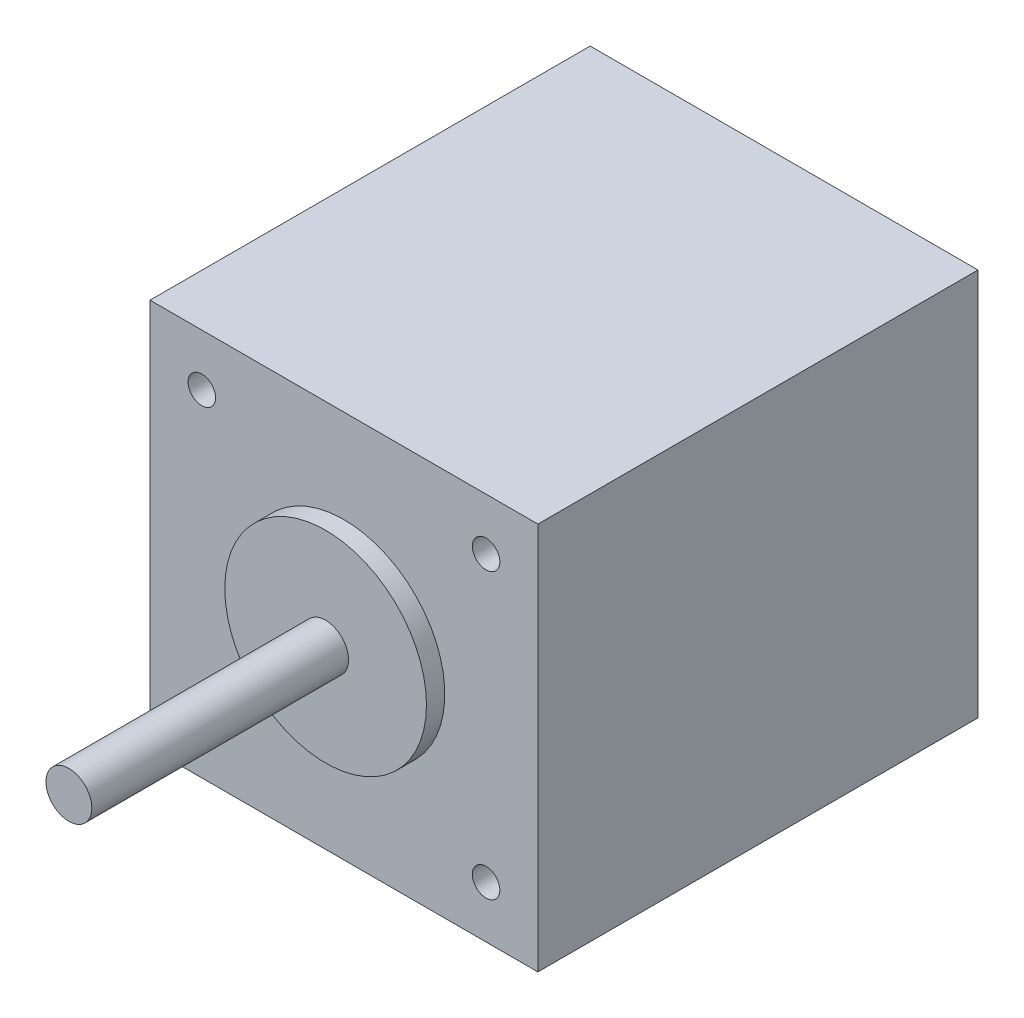
SolidWorks part; units mm, degrees
ref_plane "Спереди" through (0, 0, 0) normal (0, 0, 1) x (1, 0, 0)
ref_plane "Сверху" through (0, 0, 0) normal (0, 1, 0) x (1, 0, 0)
ref_plane "Справа" through (0, 0, 0) normal (1, 0, 0) x (0, 0, -1)
other "Configuration Table"
sketch "Эскиз1" plane through (0, 0, 0) normal (0, 0, 1) x (1, 0, 0)
  line L1 (-21.15, -21.15) -> (21.15, -21.15)
  line L2 (-21.15, -21.15) -> (-21.15, 21.15)
  line L3 (-21.15, 21.15) -> (21.15, 21.15)
  line L4 (21.15, -21.15) -> (21.15, 21.15)
  line L5 (-21.15, -21.15) -> (21.15, 21.15) construction
  line L6 (-21.15, 21.15) -> (21.15, -21.15) construction
  point P0 (0, 0)
  dimension "D1" = 42.3
  dimension "D2" = 42.3
extrude "Корпус" add sketch "Эскиз1" along normal blind 48
sketch "Эскиз2" plane through (0, 0, 0) normal (0, 0, 1) x (1, 0, 0)
  circle A0 centre (0, 0) radius 2.5
extrude "Вал_ПРЕДВ" add sketch "Эскиз2" along normal blind 78
sketch "Эскиз3" plane through (0, 0, 0) normal (0, 0, 1) x (1, 0, 0)
  circle A0 centre (0, 0) radius 11
  dimension "D1" = 22
extrude "Буртик_ПРЕДВ" add sketch "Эскиз3" along normal blind 50
sketch "Эскиз4" plane through (0, 0, 0) normal (0, 0, 1) x (1, 0, 0)
  circle A0 centre (0, 0) radius 8
  dimension "D1" = 16
sketch "Эскиз5" plane through (0, 0, 0) normal (0, 0, 1) x (1, 0, 0)
  circle A0 centre (-15.5, -15.5) radius 1.5
  circle A1 centre (-15.5, 15.5) radius 1.5
  circle A2 centre (15.5, -15.5) radius 1.5
  circle A3 centre (15.5, 15.5) radius 1.5
  dimension "D2" = 3
  dimension "D3" = 3
  dimension "D4" = 3
extrude "Крепеж_М3_ПРЕДВ" cut sketch "Эскиз5" against normal blind 4.5 from offset 48
equation "\"Мотор X ширина корпуса\"= 42.3"
equation "\"Мотор X высота корпуса\"= 42.3"
equation "\"Мотор X длина корпуса\"= 40"
equation "\"Мотор X вылет вала\"= 19.8"
equation "\"Мотор Y ширина корпуса\"= 42.3"
equation "\"Мотор Y высота корпуса\"= 42.3"
equation "\"Мотор Y длина корпуса\"= 48"
equation "\"Мотор Y вылет вала\"= 30"
equation "\"Мотор Z ширина корпуса\"= 42"
equation "\"Мотор Z высота корпуса\"= 42"
equation "\"Мотор Z длина корпуса\"= 40"
equation "\"Мотор Z вылет вала\"= 23"
equation "\"Мотор диаметр вала ПРЕДВ\"= 5"
equation "\"Мотор шаг крепления ПРЕДВ\"= 31"
equation "\"Мотор диаметр отверстий ПРЕДВ\"= 3"
equation "\"Мотор глубина отверстий ПРЕДВ\"= 4.5"
equation "\"Мотор диаметр буртика ПРЕДВ\"= 22"
equation "\"Мотор высота буртика ПРЕДВ\"= 2"
equation "\"Мотор диаметр шкива ПРЕДВ\"= 16"
equation "\"Мотор длина шкива ПРЕДВ\"= 12"
equation "\"Мотор отступ шкива ПРЕДВ\"= 5"
equation "\"Мотор X шаг градусов\"= 1.8"
equation "\"Мотор Y шаг градусов\"= 1.8"
equation "\"Мотор Z шаг градусов\"= 1.8"
equation "\"Мотор Y диаметр ротора\"= 25.78"
equation "\"D1@Эскиз1\" = \"Мотор Y ширина корпуса\""
equation "\"D1@Корпус\" = \"Мотор Y длина корпуса\""
equation "\"D1@Эскиз2\" = \"Мотор диаметр вала ПРЕДВ\""
equation "\"D1@Вал_ПРЕДВ\" = \"Мотор Y длина корпуса\" + \"Мотор Y вылет вала\""
equation "\"D1@Эскиз3\" = \"Мотор диаметр буртика ПРЕДВ\""
equation "\"D1@Буртик_ПРЕДВ\" = \"Мотор Y длина корпуса\" + \"Мотор высота буртика ПРЕДВ\""
equation "\"D1@Эскиз4\" = \"Мотор диаметр шкива ПРЕДВ\""
equation "\"D1@Эскиз5\" = \"Мотор диаметр отверстий ПРЕДВ\""
equation "\"D2@Эскиз5\" = \"Мотор диаметр отверстий ПРЕДВ\""
equation "\"D3@Эскиз5\" = \"Мотор диаметр отверстий ПРЕДВ\""
equation "\"D4@Эскиз5\" = \"Мотор диаметр отверстий ПРЕДВ\""
equation "\"D1@Крепеж_М3_ПРЕДВ\" = \"Мотор глубина отверстий ПРЕДВ\""
equation "\"D19@Крепеж_М3_ПРЕДВ\" = \"Мотор Y длина корпуса\""
equation "\"Ширина груза\"= 420"
equation "\"Глубина груза\"= 490"
equation "\"Высота груза\"= 297"
equation "\"Ширина ячейки\"= \"Ширина груза\" + 10"
equation "\"Глубина ячейки\"= \"Глубина груза\" + 10"
equation "\"Высота ячейки\"= \"Высота груза\" + 10 + 13"
equation "\"Колво ячеек ширина\"= 2"
equation "\"Колво ячеек высота\"= 2"
equation "\"Толщина стенки\" = 6"
equation "\"Крепление дверцы\"= 5 "
equation "\"Ширина рейки\"= \"Толщина шестерни\""
equation "\"Высота рейки\"= 20"
equation "\"Высота пола\"= \"Толщина стенки\" * 2"
equation "\"Колво полозьев\"= 5"
equation "\"Отступ рейки\"= 20"
equation "\"Глубина каретки\"= \"Глубина ячейки\" + 30 + \"Мотор Y высота корпуса\" + 20"
equation "\"Отступ шпильки\"= 26"
equation "\"Диаметр шпильки\"= 5"
equation "\"Длинна шпильки\"= ( \"Высота ячейки\" + \"Толщина стенки\" + \"Высота пола\" ) * \"Колво ячеек высота\" + ( \"Толщина стенки\" + \"Отступ рейки\" ) * 2 "
equation "\"Ширина пластины\"= 50  "
equation "\"Высота зона выгрузки\"= \"Высота ячейки\" * 2 + \"Толщина стенки\" * 2"
equation "\"Колво выгрузки\"= 1"
equation "\"Отступ крепления мотора фиксации\" = 30"
equation "\"Ширина ячейки выгрузки\"= \"Ширина ячейки\" + \"Толщина стенки\" + \"Отступ крепления мотора фиксации\"*2"
equation "\"Длинна рейки\"= ( \"Ширина ячейки\" + \"Толщина стенки\" + \"Крепление дверцы\" ) * \"Колво ячеек ширина\" + \"Ширина ячейки выгрузки\" * \"Колво выгрузки\" + \"Толщина стенки\""
equation "\"Толщина шестерни\"= 10"
